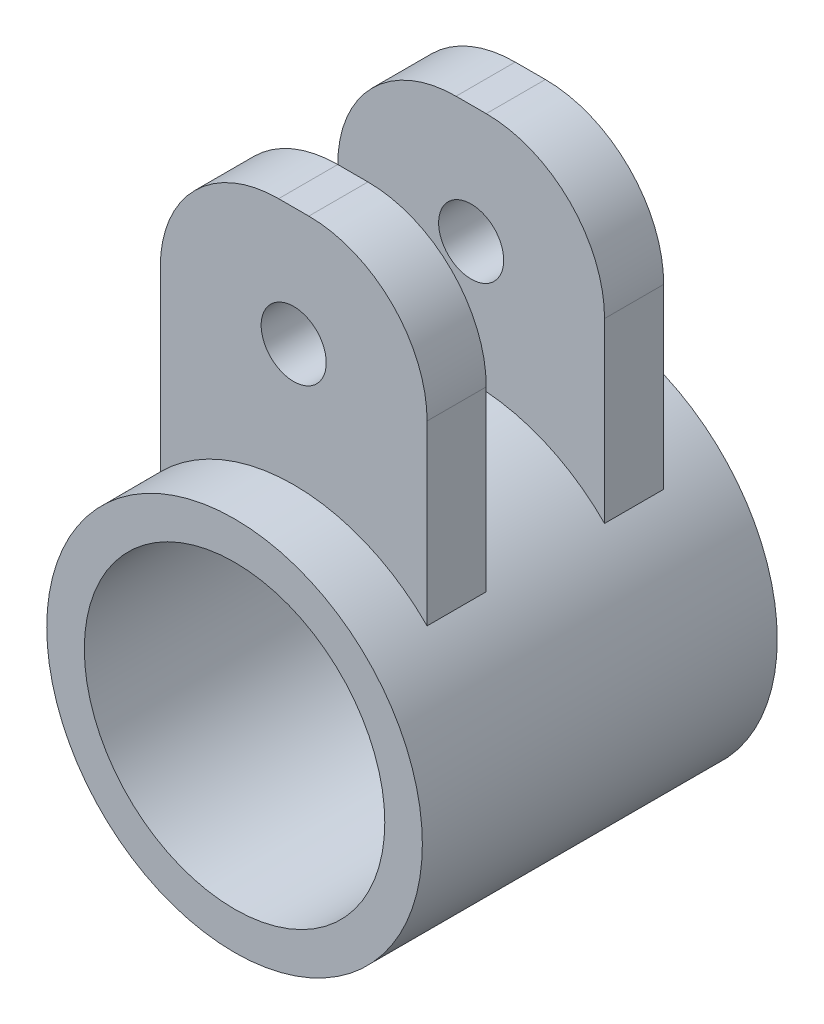
SolidWorks part; units mm, degrees
material "1060 Alloy"
ref_plane "Front Plane" through (0, 0, 0) normal (0, 0, 1) x (1, 0, 0)
ref_plane "Top Plane" through (0, 0, 0) normal (0, 1, 0) x (1, 0, 0)
ref_plane "Right Plane" through (0, 0, 0) normal (1, 0, 0) x (0, 0, -1)
sketch "Sketch1" plane through (0, 0, 0) normal (0, 0, 1) x (1, 0, 0)
  circle A0 centre (0, 0) radius 12.7
  circle A1 centre (0, 0) radius 15.875
  dimension "D1" = 31.75
  dimension "D2" = 25.4
extrude "Boss-Extrude1" add sketch "Sketch1" along normal mid plane 30
sketch "Sketch3" plane through (0, 0, 0) normal (0, 0, 1) x (1, 0, 0)
  line L2 (-11.2764, 11.174) -> (-11.2764, 26.174)
  line L3 (-1.2764, 36.174) -> (1.2764, 36.174)
  line L4 (11.2764, 11.174) -> (11.2764, 26.174)
  circle A0 centre (0, 0) radius 15.875 construction
  arc A1 (11.2764, 11.174) -> (-11.2764, 11.174) centre (0, 0) ccw
  arc A2 (-11.2764, 26.174) -> (-1.2764, 36.174) centre (-1.2764, 26.174) cw
  arc A3 (1.2764, 36.174) -> (11.2764, 26.174) centre (1.2764, 26.174) cw
  point P9 (-11.2764, 36.174)
  dimension "D2" = 10
  dimension "D1" = 25
extrude "Boss-Extrude2" add sketch "Sketch3" along normal mid plane 20
extrude "Cut-Extrude1" cut sketch "Sketch3<2>" against normal mid plane 10
sketch "Sketch3<2>" plane through (0, 0, 0) normal (0, 0, 1) x (1, 0, 0) same geometry as "Sketch3"
sketch "Sketch4" plane through (0, 0, 10) normal (0, 0, 1) x (1, 0, 0)
  line L0 (0, 36.174) -> (0, 26.174) construction
  line L1 (1.2764, 36.174) -> (-1.2764, 36.174) construction
  dimension "D1" = 10
hole_wizard "M5 Clearance Hole1" positions "Sketch5" profile "Sketch6" hole size "M5" standard "AS" end condition through all
sketch "Sketch5" plane through (0, 0, 10) normal (0, 0, 1) x (1, 0, 0)
  point P0 (0, 26.174)
sketch "Sketch6" plane through (0, 26.174, 10) normal (1, 0, 0) x (0, -1, 0)
  line L0 (0, 0) -> (0, 25)
  line L1 (0, 25) -> (2.75, 25)
  line L2 (2.75, 25) -> (2.75, 0)
  line L5 (2.75, 0) -> (0, 0)
  line L11 (0, -6.35) -> (0, 107.95) construction
  dimension "Thru Hole Dia." = 5.5
  dimension "Thru Hole Depth" = 25
equation "\"keelOutDiameter\"= 1in"
equation "\"keelInDiameter\"= \"keelOutDiameter\" - 0.125in"
equation "\"frontBoltClearance\"= 7.25mm"
equation "\"betweenBoltsDistance\"= 20mm"
equation "\"wingLength\"= 1.4m"
equation "\"frontTubeLength\"= \"wingLength\" / sin ( 34.95deg )"
equation "\"plateThickness\"= 5mm"
equation "\"crossBarOutDiameter\"= 1in"
equation "\"crossBarInDiameter\"= \"crossBarOutDiameter\" - 0.125in"
equation "\"frontToCrossBar\"= 466mm"
